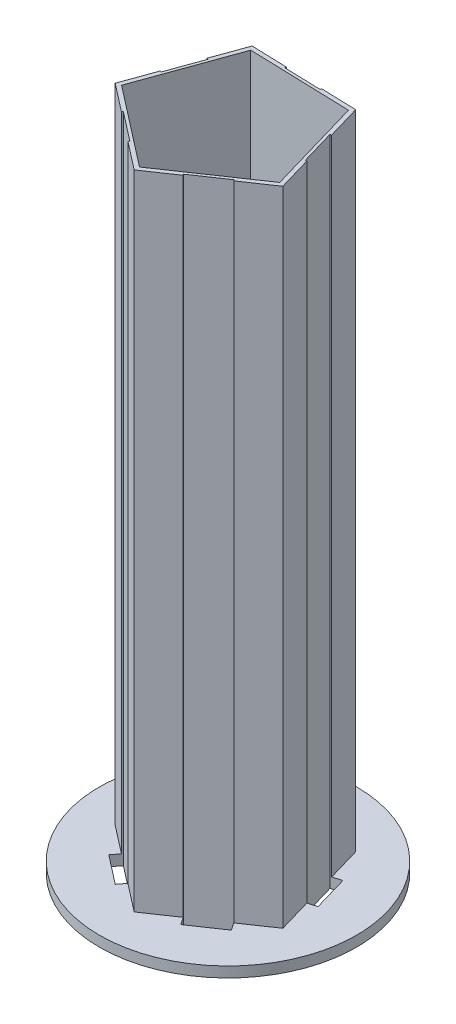
SolidWorks part; units mm, degrees
ref_plane "Front Plane" through (0, 0, 0) normal (0, 0, 1) x (1, 0, 0)
ref_plane "Top Plane" through (0, 0, 0) normal (0, 1, 0) x (1, 0, 0)
ref_plane "Right Plane" through (0, 0, 0) normal (1, 0, 0) x (0, 0, -1)
sketch "Sketch1" plane through (0, 0, 0) normal (0, 1, 0) x (1, 0, 0)
  circle A0 centre (0, 0) radius 37
  dimension "D1" = 74
extrude "Boss-Extrude1" add sketch "Sketch1" along normal blind 3
sketch "Sketch2" plane through (0, 3, 0) normal (0, 1, 0) x (1, 0, 0)
  line L0 (16.0579, 20.7082) -> (-14.7325, 21.6711)
  line L1 (23.2611, -8.3705) -> (15.1489, 19.536)
  line L2 (15.1489, 19.536) -> (-13.8986, 20.4445)
  line L3 (-13.8986, 20.4445) -> (-23.7387, -6.9006)
  line L4 (-23.7387, -6.9006) -> (-0.7728, -24.7093)
  line L5 (-0.7728, -24.7093) -> (23.2611, -8.3705)
  line L6 (-14.7325, 21.6711) -> (-25.163, -7.3147)
  line L7 (-25.163, -7.3147) -> (-0.8191, -26.1918)
  line L8 (-0.8191, -26.1918) -> (24.6568, -8.8728)
  line L9 (24.6568, -8.8728) -> (16.0579, 20.7082)
  circle A0 centre (0, 0) radius 20 construction
  dimension "D1" = 40
  dimension "D2" = 1.2
extrude "Boss-Extrude2" add sketch "Sketch2" along normal blind 185
sketch "Sketch3" plane through (0.6627, 0, -21.1896) normal (0.0313, 0, -0.9995) x (-0.9995, 0, -0.0313)
  line L0 (-15.4027, 3) -> (15.4027, 3) construction
  line L1 (-5.25, 188) -> (5.25, 188)
  line L2 (-5.25, 188) -> (-5.25, 3)
  line L3 (-5.25, 3) -> (5.25, 3)
  line L4 (5.25, 188) -> (5.25, 3)
  line L5 (-5.25, 188) -> (5.25, 3) construction
  line L6 (-5.25, 3) -> (5.25, 188) construction
  line L7 (-15.4027, 188) -> (15.4027, 188) construction
  point P0 (0, 95.5)
  point P7 (0, 3)
  point P10 (0, 0)
  dimension "D1" = 10.5
extrude "Cut-Extrude1" cut sketch "Sketch3" against normal blind 0.4
pattern_circular "CirPattern1" count 5 over 360 about axis through (0, 3, 0) along (0, -1, 0) of "Cut-Extrude1"
sketch "Sketch4" plane through (0, 3, 0) normal (0, 1, 0) x (1, 0, 0)
  line L0 (-17.7938, 11.9827) -> (-21.349, 2.1029)
  line L1 (-17.7938, 11.9827) -> (-20.6166, 12.9985)
  line L2 (-21.349, 2.1029) -> (-24.1718, 3.1187)
  line L3 (-20.6166, 12.9985) -> (-24.1718, 3.1187)
  dimension "D1" = 3
extrude "Cut-Extrude2" cut sketch "Sketch4" against normal up to surface (3 mm away) up to face at (0, 0, 37)
pattern_circular "CirPattern2" count 5 over 360 about axis through (0, 3, 0) along (0, -1, 0) of "Cut-Extrude2"
